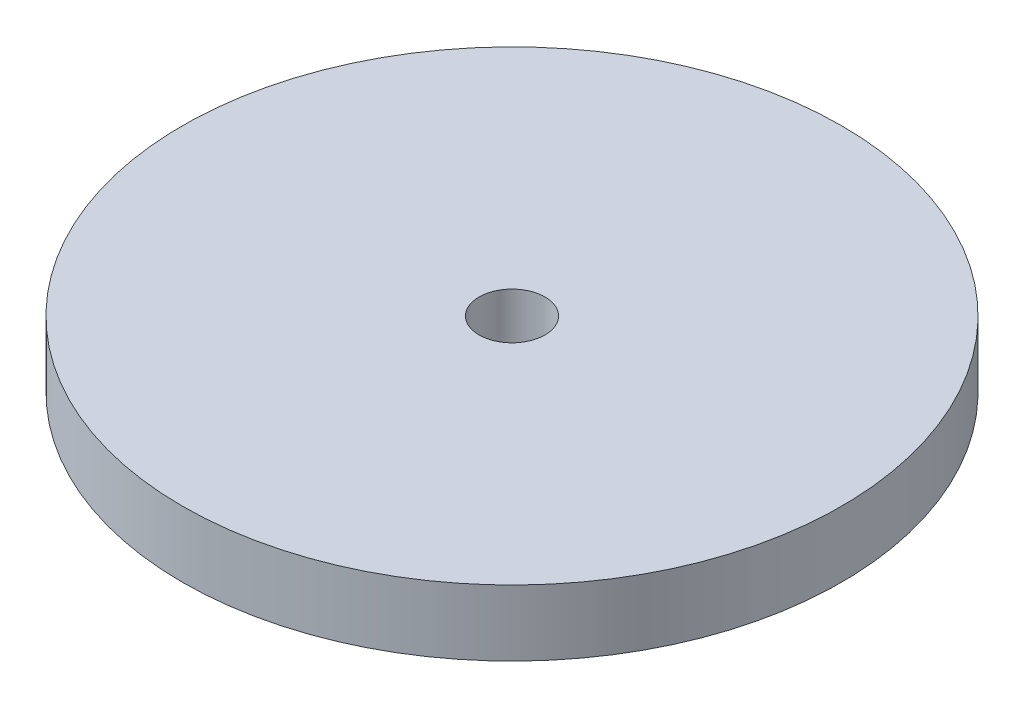
SolidWorks part; units mm, degrees
ref_plane "Front Plane" through (0, 0, 0) normal (0, 0, 1) x (1, 0, 0)
ref_plane "Top Plane" through (0, 0, 0) normal (0, 1, 0) x (1, 0, 0)
ref_plane "Right Plane" through (0, 0, 0) normal (1, 0, 0) x (0, 0, -1)
sketch "Sketch1" plane through (0, 0, 0) normal (0, 1, 0) x (1, 0, 0)
  line L0 (0, -38.1) -> (0, 47.0942) construction
  line L4 (44.7892, 14.5529) -> (0, 47.0942) construction
  line L5 (0, 47.0942) -> (-44.7892, 14.5529) construction
  line L6 (-44.7892, 14.5529) -> (36.2353, -11.7735) construction
  line L7 (44.7892, 14.5529) -> (-36.3649, -11.3712) construction
  line L8 (-27.6813, -38.1) -> (22.3946, 30.8235) construction
  line L9 (-44.7892, 14.5529) -> (-27.6813, -38.1) [skipped]
  line L10 (-27.6813, -38.1) -> (27.6813, -38.1) [skipped]
  line L11 (27.6813, -38.1) -> (44.7892, 14.5529) [skipped]
  line L12 (-31.5904, -3.1799) -> (0, 0) construction
  line L13 (0, 0) -> (-27.8167, -15.3066) construction
  line L14 (-31.5904, -3.1799) -> (-27.8167, -15.3066) construction
  circle A0 centre (0, 0) radius 31.75
  dimension "D1" = 63.5
  dimension "D2" = 6.35
  dimension "D3" = 6.35
extrude "Boss-Extrude1" add sketch "Sketch1" along normal blind 6.35
sketch "Sketch2" plane through (0, 6.35, 0) normal (0, 1, 0) x (1, 0, 0)
  circle A0 centre (0, 0) radius 3.175
  dimension "D1" = 6.35
extrude "Cut-Extrude1" cut sketch "Sketch2" against normal through all
